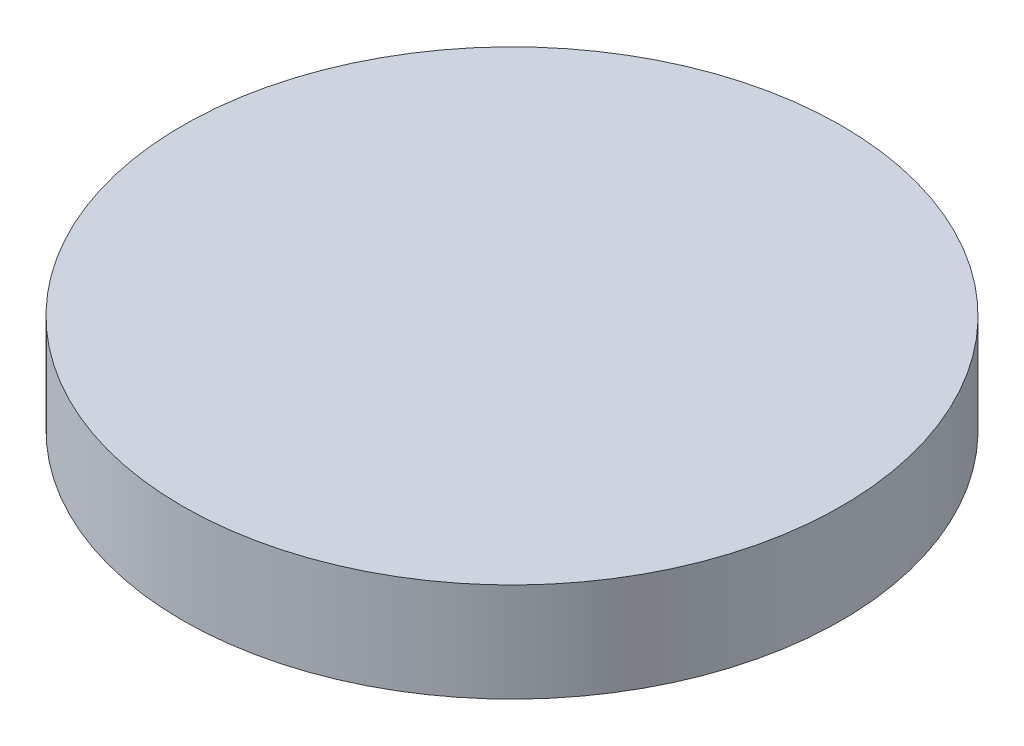
SolidWorks part; units mm, degrees
ref_plane "Front" through (0, 0, 0) normal (0, 0, 1) x (1, 0, 0)
ref_plane "Top" through (0, 0, 0) normal (0, 1, 0) x (1, 0, 0)
ref_plane "Right" through (0, 0, 0) normal (1, 0, 0) x (0, 0, -1)
sketch "Sketch1" plane through (0, 0, 0) normal (0, 1, 0) x (1, 0, 0)
  circle A0 centre (0, 0) radius 10
extrude "Boss-Extrude1" add sketch "Sketch1" along normal blind 3
